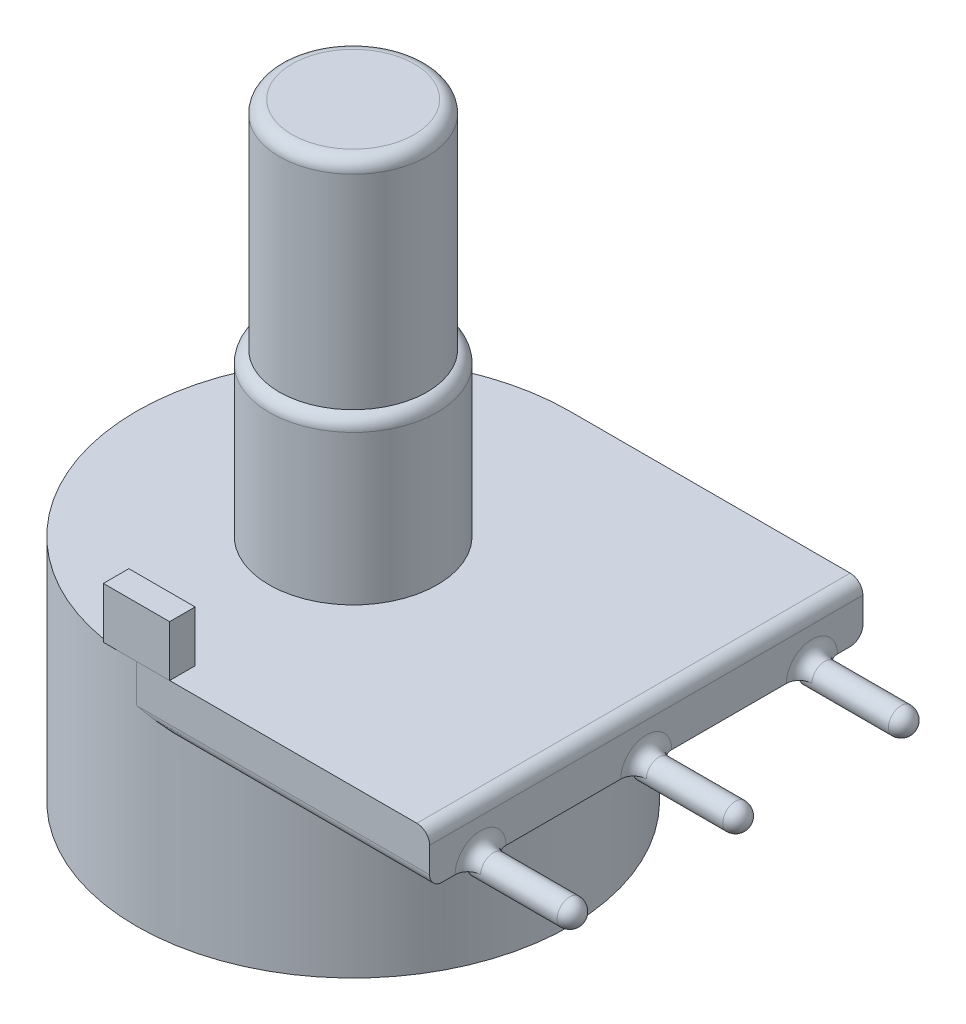
SolidWorks part; units mm, degrees
material "Copper"
ref_plane "Front Plane" through (0, 0, 0) normal (0, 0, 1) x (1, 0, 0)
ref_plane "Top Plane" through (0, 0, 0) normal (0, 1, 0) x (1, 0, 0)
ref_plane "Right Plane" through (0, 0, 0) normal (1, 0, 0) x (0, 0, -1)
sketch "Sketch1" plane through (0, 0, 0) normal (0, 1, 0) x (1, 0, 0)
  circle A0 centre (0, 0) radius 8.5
  dimension "D1" = 17
extrude "Boss-Extrude1" add sketch "Sketch1" along normal blind 9
sketch "Sketch2" plane through (0, 9, 0) normal (0, 1, 0) x (1, 0, 0)
  line L0 (0, 8.5) -> (11.5, 8.5)
  line L1 (11.5, 8.5) -> (11.5, -8.5)
  line L2 (11.5, -8.5) -> (0, -8.5)
  circle A1 centre (0, 0) radius 8.5
  arc A2 (0, 8.5) -> (0, -8.5) centre (0, 0) ccw
  point P5 (-8.5, 0)
  dimension "D2" = 20
  dimension "D1" = 0
extrude "Boss-Extrude2" add sketch "Sketch2" against normal blind 2
sketch "Sketch3" plane through (0, 9, 0) normal (0, -1, 0) x (1, 0, 0)
  circle A0 centre (0, 0) radius 3.3
  dimension "D1" = 6.6
extrude "Boss-Extrude3" add sketch "Sketch3" against normal blind 6.35
sketch "Sketch4" plane through (0, 15.35, 0) normal (0, 1, 0) x (-1, 0, 0)
  circle A0 centre (0, 0) radius 2.9
  dimension "D1" = 5.8
extrude "Boss-Extrude4" add sketch "Sketch4" along normal blind 8.5
sketch "Sketch5" plane through (11.5, 0, 0) normal (1, 0, 0) x (0, 0, -1)
  line L0 (-8.5, 7) -> (8.5, 7) construction
  line L1 (0, 9) -> (0, 7) construction
  line L2 (-8.5, 9) -> (8.5, 9) construction
  line L3 (-8.5, 7) -> (-8.5, 9) construction
  circle A0 centre (-6.5, 7) radius 0.5
  circle A1 centre (0, 7) radius 0.5
  circle A2 centre (6.5, 7) radius 0.5
  dimension "D1" = 1
  dimension "D2" = 2
extrude "Boss-Extrude5" add sketch "Sketch5" along normal blind 4
sketch "Sketch7" plane through (0, 9, 0) normal (0, 1, 0) x (1, 0, 0)
  line L0 (0, 0) -> (0, 3.3) construction
  line L1 (-1.3, -7.5) -> (1.3, -7.5)
  line L2 (-1.3, -7.5) -> (-1.3, -8.5)
  line L3 (-1.3, -8.5) -> (1.3, -8.5)
  line L4 (1.3, -7.5) -> (1.3, -8.5)
  line L5 (0, 3.3) -> (0, -7.5) construction
  line L6 (0, -8.5) -> (11.5, -8.5) construction
  circle A0 centre (0, 0) radius 3.3 construction
  dimension "D2" = 1
  dimension "D3" = 2.6
extrude "Boss-Extrude6" add sketch "Sketch7" along normal blind 2 separate body
fillet "Fillet1" radius 0.5 11 edges at (11.5, 7.5, 6.5) (15.5, 7, 6) (11.5, 7.5, 0) (15.5, 7, -0.5) (11.5, 7.5, -6.5) (15.5, 7, -6) (11.5, 9, 0) (0, 23.85, 2.9) (0, 15.35, -3.3) (5.75, 7, 8.5) (5.75, 7, -8.5)
